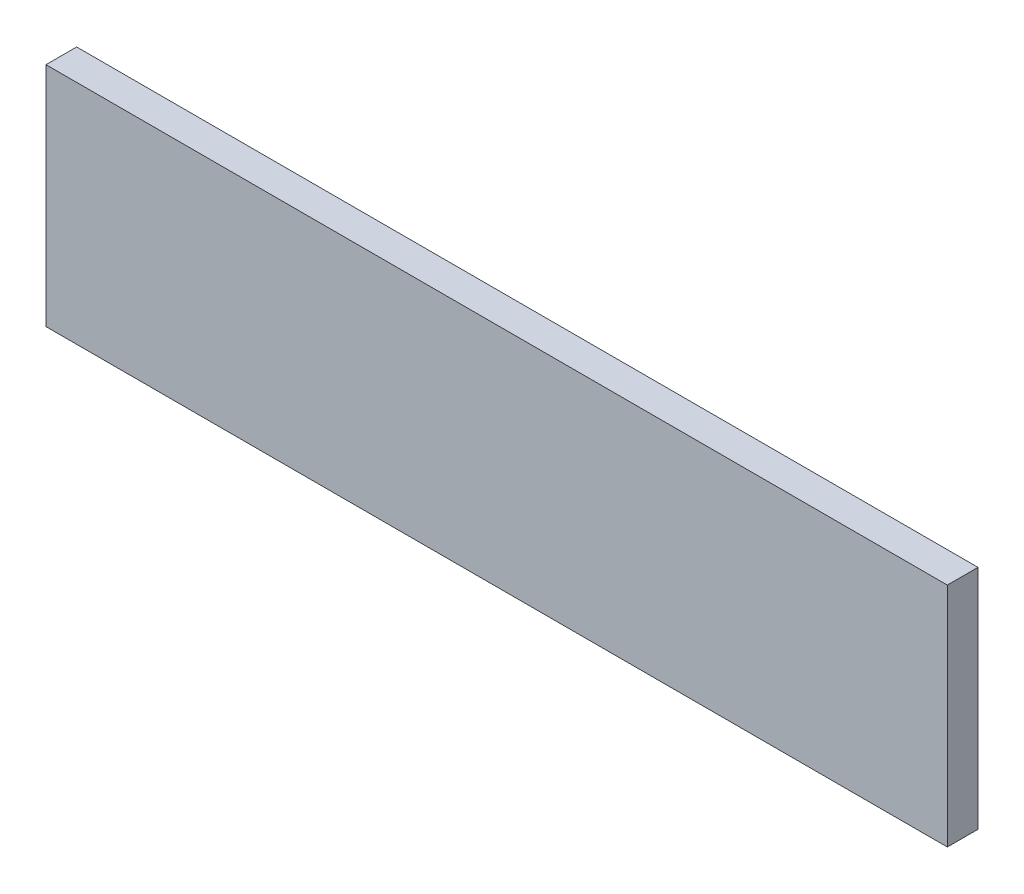
SolidWorks part; units mm, degrees
material "Plain Carbon Steel"
ref_plane "Front Plane" through (0, 0, 0) normal (0, 0, 1) x (1, 0, 0)
ref_plane "Top Plane" through (0, 0, 0) normal (0, 1, 0) x (1, 0, 0)
ref_plane "Right Plane" through (0, 0, 0) normal (1, 0, 0) x (0, 0, -1)
sketch "Sketch1" plane through (0, 0, 0) normal (0, 0, 1) x (1, 0, 0)
  line L0 (-67, -7) -> (-67, 67) construction
  line L1 (-67, 67) -> (227, 67)
  line L2 (-67, 67) -> (-67, -7)
  line L3 (-67, -7) -> (227, -7)
  line L4 (227, 67) -> (227, -7)
  line L5 (-67, 67) -> (227, 67) construction
  line L6 (227, 67) -> (227, -7) construction
  line L7 (227, -7) -> (-67, -7) construction
extrude "Boss-Extrude1" add sketch "Sketch1" along normal blind 10
